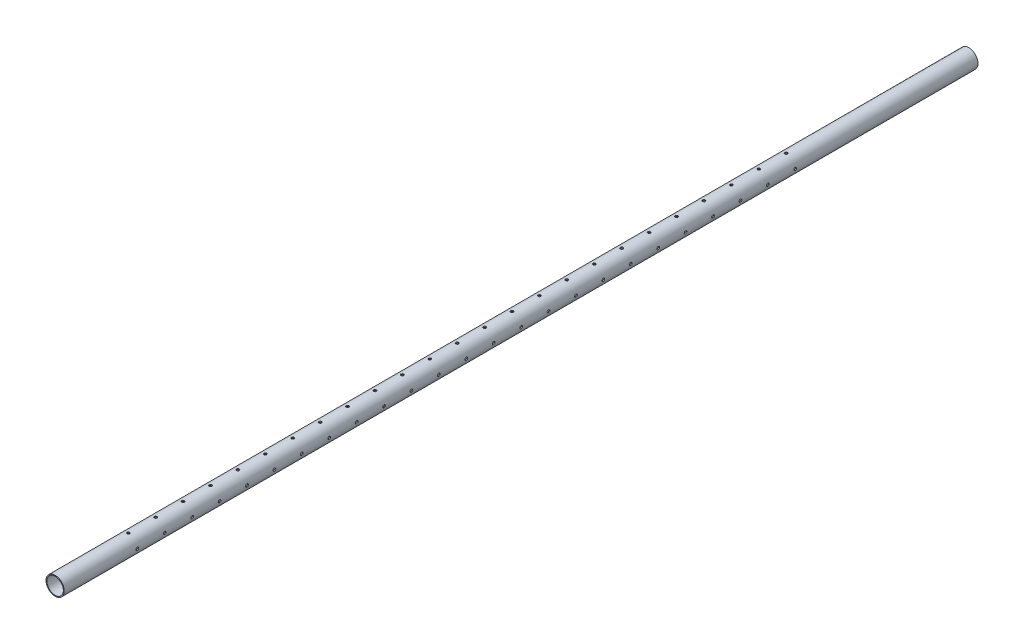
SolidWorks part; units mm, degrees
ref_plane "Front Plane" through (0, 0, 0) normal (0, 0, 1) x (1, 0, 0)
ref_plane "Top Plane" through (0, 0, 0) normal (0, 1, 0) x (1, 0, 0)
ref_plane "Right Plane" through (0, 0, 0) normal (1, 0, 0) x (0, 0, -1)
sketch "Sketch1" plane through (0, 0, 0) normal (0, 0, 1) x (1, 0, 0)
  circle A0 centre (0, 0) radius 10
  circle A1 centre (0, 0) radius 9
  dimension "D1" = 20
  dimension "D2" = 18
extrude "Boss-Extrude1" add sketch "Sketch1" along normal blind 1000
ref_plane "Plane1" through (0, 10, 0) normal (0, 1, 0) x (1, 0, 0)
sketch "Sketch4" plane through (0, 10, 0) normal (0, 1, 0) x (1, 0, 0)
  point P0 (0, -200)
  point P11 (0, -230)
  point P12 (0, -260)
  point P13 (0, -290)
  point P14 (0, -320)
  point P15 (0, -350)
  point P16 (0, -380)
  point P17 (0, -410)
  point P18 (0, -440)
  point P19 (0, -470)
  point P20 (0, -500)
  point P21 (0, -530)
  point P22 (0, -560)
  point P23 (0, -590)
  point P24 (0, -620)
  point P25 (0, -650)
  point P26 (0, -680)
  point P27 (0, -710)
  point P28 (0, -740)
  point P29 (0, -770)
  point P30 (0, -800)
  point P31 (0, -830)
  point P32 (0, -860)
  point P33 (0, -890)
  point P34 (0, -920)
  dimension "D1" = 200
  dimension "D2" = 25
hole_wizard "Ø3.0mm Dowel Hole1" positions "Sketch4" profile "Sketch3" hole size "Ø3.0" standard "DIN" end condition through all
sketch "Sketch3" plane through (0, 10, 200) normal (1, 0, 0) x (0, 0, 1)
  line L0 (0, 0) -> (0, 20)
  line L1 (0, 20) -> (1.5, 20)
  line L2 (1.5, 20) -> (1.5, 0)
  line L5 (1.5, 0) -> (0, 0)
  line L11 (0, -6.35) -> (0, 107.95) construction
  dimension "Thru Hole Dia." = 3
  dimension "Thru Hole Depth" = 20
ref_plane "Plane2" through (10, 0, 0) normal (1, 0, 0) x (0, 0, -1)
sketch "Sketch7" plane through (10, 0, 0) normal (1, 0, 0) x (0, 0, -1)
  line L0 (11, 0) -> (-11, 0) construction
  point P0 (-200, 0)
  point P10 (-230, 0)
  point P11 (-260, 0)
  point P12 (-290, 0)
  point P13 (-320, 0)
  point P14 (-350, 0)
  point P15 (-380, 0)
  point P16 (-410, 0)
  point P17 (-440, 0)
  point P18 (-470, 0)
  point P19 (-500, 0)
  point P20 (-530, 0)
  point P21 (-560, 0)
  point P22 (-590, 0)
  point P23 (-620, 0)
  point P24 (-650, 0)
  point P25 (-680, 0)
  point P26 (-710, 0)
  point P27 (-740, 0)
  point P28 (-770, 0)
  point P29 (-800, 0)
  point P30 (-830, 0)
  point P31 (-860, 0)
  point P32 (-890, 0)
  point P33 (-920, 0)
  dimension "D1" = 200
  dimension "D2" = 25
hole_wizard "Ø3.0mm Dowel Hole2" positions "Sketch7" profile "Sketch6" hole size "Ø3.0" standard "DIN" end condition through all
sketch "Sketch6" plane through (10, 0, 200) normal (0, 1, 0) x (0, 0, -1)
  line L0 (0, 0) -> (0, 20)
  line L1 (0, 20) -> (1.5, 20)
  line L2 (1.5, 20) -> (1.5, 0)
  line L5 (1.5, 0) -> (0, 0)
  line L11 (0, -6.35) -> (0, 107.95) construction
  dimension "Thru Hole Dia." = 3
  dimension "Thru Hole Depth" = 20
